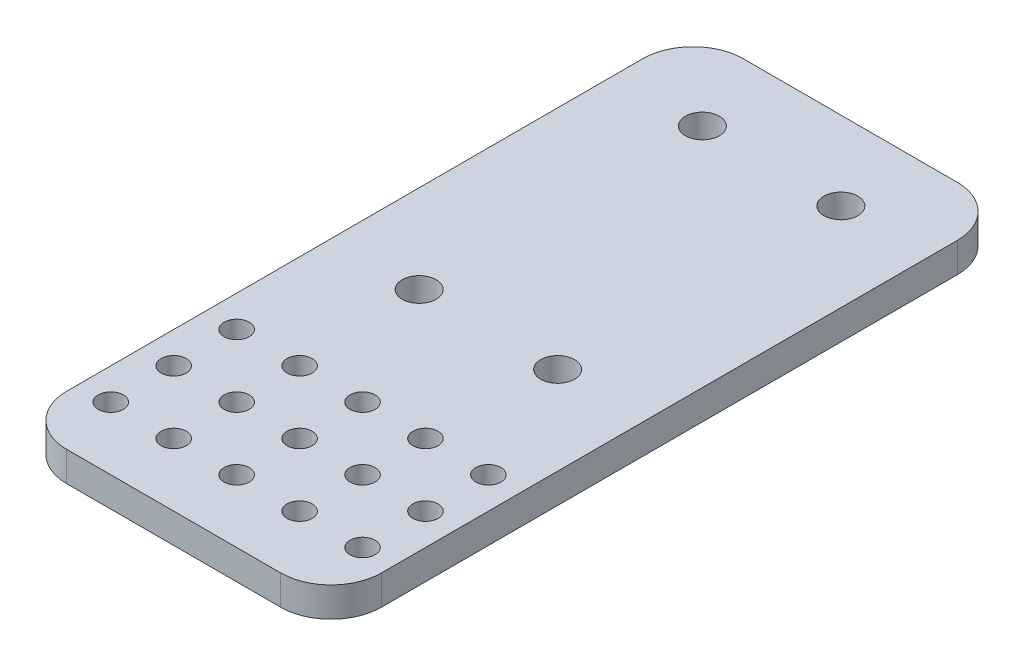
SolidWorks part; units mm, degrees
other "Markup1"
sketch "Sketch3" plane through (0, 6, 0) normal (-0.2556, 0.7181, 0.6473) x (0.9665, 0.2047, 0.1545)
sketch "Sketch5" plane through (0, 6, 0) normal (-0.2556, 0.7181, 0.6473) x (0.9665, 0.2047, 0.1545)
ref_plane "Front Plane" through (0, 0, 0) normal (0, 0, 1) x (1, 0, 0)
ref_plane "Top Plane" through (0, 0, 0) normal (0, 1, 0) x (1, 0, 0)
ref_plane "Right Plane" through (0, 0, 0) normal (1, 0, 0) x (0, 0, -1)
sketch "Sketch1" plane through (0, 0, 0) normal (0, 1, 0) x (1, 0, 0)
  line L0 (31.75, 136.525) -> (31.75, 0) construction
  line L1 (0, 0) -> (63.5, 0)
  line L2 (0, 0) -> (0, 136.525)
  line L3 (0, 136.525) -> (63.5, 136.525)
  line L4 (63.5, 0) -> (63.5, 136.525)
  line L5 (57.15, 12.7) -> (44.45, 12.7) construction
  line L6 (57.15, 12.7) -> (57.15, 25.4) construction
  circle A0 centre (17.78, 120.65) radius 3.429 construction
  circle A1 centre (45.72, 63.5) radius 3.429 construction
  circle A2 centre (17.78, 63.5) radius 3.429 construction
  circle A3 centre (45.72, 120.65) radius 3.429 construction
  circle A4 centre (57.15, 12.7) radius 2.54
  circle A5 centre (44.45, 12.7) radius 2.54
  circle A6 centre (31.75, 12.7) radius 2.54
  circle A7 centre (19.05, 12.7) radius 2.54
  circle A8 centre (44.45, 25.4) radius 2.54
  circle A9 centre (31.75, 25.4) radius 2.54
  circle A10 centre (19.05, 25.4) radius 2.54
  circle A11 centre (44.45, 38.1) radius 2.54
  circle A12 centre (31.75, 38.1) radius 2.54
  circle A13 centre (19.05, 38.1) radius 2.54
  circle A14 centre (57.15, 25.4) radius 2.54
  circle A15 centre (57.15, 38.1) radius 2.54
  circle A16 centre (6.35, 12.7) radius 2.54
  circle A17 centre (6.35, 25.4) radius 2.54
  circle A18 centre (6.35, 38.1) radius 2.54
  dimension "D3" = 57.15
  dimension "D4" = 27.94
  dimension "D5" = 6.858
  dimension "D6" = 15.875
  dimension "D7" = 17.78
  dimension "D8" = 12.7
  dimension "D9" = 6.35
  dimension "D10" = 5.08
  dimension "D2" = 25.4
  dimension "D1" = 63.5
  dimension "D13" = 12.7
  dimension "D14" = 12.7
  dimension "D11" = 5
  dimension "D12" = 3
extrude "Boss-Extrude1" add sketch "Sketch1" along normal blind 6 contours L4 L3 L2 region at (31.75, 0, -69.8203)
fillet "Fillet1" radius 10.16 4 edges at (0, 3, -136.525) (63.5, 3, -136.525) (63.5, 3, 0) (0, 3, 0)
sketch "Sketch6" plane through (0, 6, 0) normal (0, 1, 0) x (1, 0, 0)
  circle A0 centre (17.78, 120.65) radius 3.429 construction
  circle A1 centre (45.72, 120.65) radius 3.429 construction
  circle A2 centre (17.78, 63.5) radius 3.429 construction
  circle A3 centre (45.72, 63.5) radius 3.429 construction
  circle A4 centre (17.78, 120.65) radius 3.429
  circle A5 centre (45.72, 120.65) radius 3.429
  circle A6 centre (17.78, 63.5) radius 3.429
  circle A7 centre (45.72, 63.5) radius 3.429
extrude "Cut-Extrude2" cut sketch "Sketch6" against normal through all
sketch "Sketch4" plane through (0, 0, 0) normal (0, -1, 0) x (-1, 0, 0)
  line L1 (-63.5, 10.16) -> (-63.5, 126.365) construction
  line L2 (-63.5, -1000) -> (-63.5, 49000) construction
  line L4 (-1076.9756, 0) -> (48923.0244, 0) construction
  line L6 (-10.16, 0) -> (-53.34, 0) construction
  point P2 (-63.5, -4.8279)
  point P6 (-63.5, 0)
